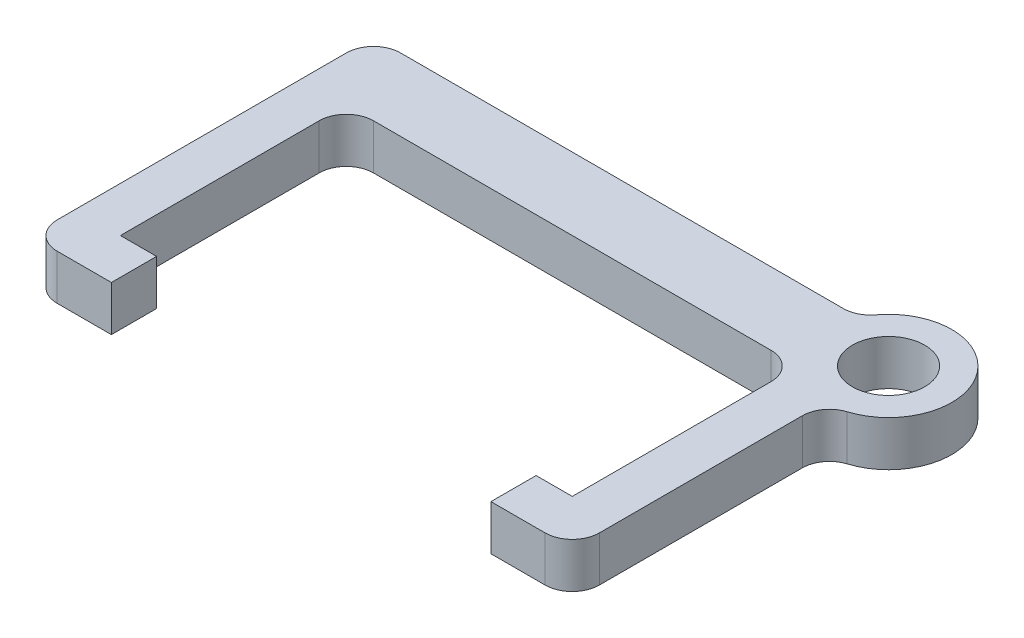
SolidWorks part; units mm, degrees
ref_plane "Front Plane" through (0, 0, 0) normal (0, 0, 1) x (1, 0, 0)
ref_plane "Top Plane" through (0, 0, 0) normal (0, 1, 0) x (1, 0, 0)
ref_plane "Right Plane" through (0, 0, 0) normal (1, 0, 0) x (0, 0, -1)
sketch "Sketch1" plane through (0, 0, 0) normal (0, 1, 0) x (1, 0, 0)
  line L0 (8, 0) -> (52, 0)
  line L2 (0, 2) -> (0, -27)
  line L3 (3, -30) -> (9, -30)
  line L4 (9, -30) -> (9, -25)
  line L5 (9, -25) -> (5, -25)
  line L6 (5, -3) -> (5, -25)
  line L7 (5, 5) -> (5, -30) construction
  line L9 (60, -4.5394) -> (60, -27)
  line L10 (55, -3) -> (55, -25)
  line L11 (55, -30) -> (57, -30)
  line L12 (55, 5) -> (55, -30) construction
  line L13 (55, -30) -> (51, -30)
  line L14 (60, 5) -> (60, -30) construction
  line L15 (0, 5) -> (0, -30) construction
  line L16 (3, 8) -> (52, 8)
  line L17 (51, -30) -> (51, -25)
  line L18 (0, 2) -> (0, 5)
  line L19 (51, -25) -> (55, -25)
  circle A0 centre (60, 5) radius 4
  arc A1 (55, 0.101) -> (55.101, 0) centre (60, 5) ccw
  circle A2 centre (60, 5) radius 7 construction
  arc A3 (62.1, -1.6776) -> (54.4, 9.2) centre (60, 5) ccw
  arc A5 (55, -3) -> (52, 0) centre (52, -3) ccw
  arc A6 (8, 0) -> (5, -3) centre (8, -3) ccw
  arc A7 (3, -30) -> (0, -27) centre (3, -27) cw
  arc A9 (62.1, -1.6776) -> (60, -4.5394) centre (63, -4.5394) ccw
  arc A11 (54.4, 9.2) -> (52, 8) centre (52, 11) cw
  arc A12 (3, 8) -> (0, 5) centre (3, 5) ccw
  arc A13 (60, -27) -> (57, -30) centre (57, -27) cw
  point P33 (0, -30)
  dimension "D6" = 3
  dimension "D7" = 4
  dimension "D2" = 3
  dimension "D8" = 3
  dimension "D10" = 3
  dimension "D1" = 5
  dimension "D3" = 5
  dimension "D4" = 9
  dimension "D9" = 5
  dimension "D5" = 5
extrude "Boss-Extrude1" add sketch "Sketch1" along normal blind 5 contours A3 L2 A7 L3 L4 L5 L6 A6 L0 A5 L10 L11 L9 A9 A0 region at (5.3195, 0, 0.3195)
